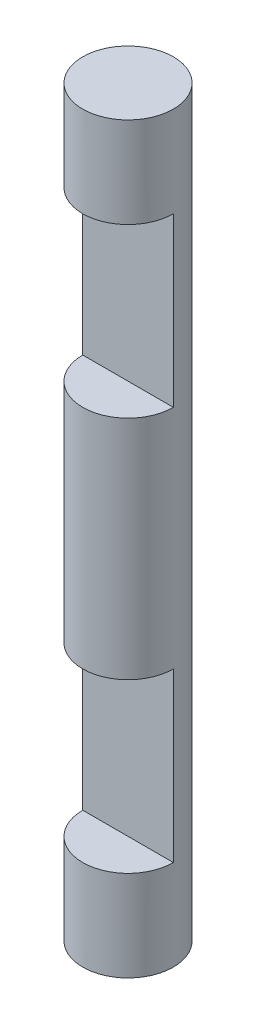
SolidWorks part; units mm, degrees
material "ABS"
ref_plane "Front Plane" through (0, 0, 0) normal (0, 0, 1) x (1, 0, 0)
ref_plane "Top Plane" through (0, 0, 0) normal (0, 1, 0) x (1, 0, 0)
ref_plane "Right Plane" through (0, 0, 0) normal (1, 0, 0) x (0, 0, -1)
sketch "Sketch1" plane through (0, 0, 0) normal (0, 1, 0) x (1, 0, 0)
  circle A0 centre (0, 0) radius 13
  dimension "D1" = 26
extrude "Boss-Extrude1" add sketch "Sketch1" along normal blind 1
ref_plane "Plane1" through (0, 1, 0) normal (0, 1, 0) x (1, 0, 0)
ref_plane "Plane2" through (0, 4.7, 0) normal (0, 1, 0) x (1, 0, 0)
ref_plane "Plane3" through (0, 9.7, 0) normal (0, 1, 0) x (1, 0, 0)
ref_plane "Plane4" through (0, 13.4, 0) normal (0, 1, 0) x (1, 0, 0)
ref_plane "Plane5" through (0, 18.4, 0) normal (0, 1, 0) x (1, 0, 0)
ref_plane "Plane6" through (0, 22.1, 0) normal (0, 1, 0) x (1, 0, 0)
ref_plane "Plane7" through (0, 27.1, 0) normal (0, 1, 0) x (1, 0, 0)
ref_plane "Plane8" through (0, 30.8, 0) normal (0, 1, 0) x (1, 0, 0)
sketch "Sketch16" plane through (0, 30.8, 0) normal (0, 1, 0) x (1, 0, 0)
  circle A0 centre (0, 0) radius 13
  circle A1 centre (0, 0) radius 13 construction
  dimension "D1" = 0
extrude "Boss-Extrude3" add sketch "Sketch16" along normal blind 1 separate body
sketch "Sketch18" plane through (0, 4.7, 0) normal (0, 1, 0) x (1, 0, 0)
  line L1 (-11, -11) -> (11, -11)
  line L2 (-11, -11) -> (-11, 11)
  line L3 (-11, 11) -> (11, 11)
  line L4 (11, -11) -> (11, 11)
  dimension "D2" = 22
  dimension "D3" = 22
sketch "Sketch19" plane through (0, 1, 0) normal (0, 1, 0) x (1, 0, 0)
  circle A0 centre (0, 11) radius 1
  point P13 (0, 0)
  dimension "D1" = 2
  dimension "D2" = 11
extrude "Boss-Extrude4" add sketch "Sketch19" along normal up to surface (29.8 mm away) up to face at (0, 30.8, 13)
extrude "Cut-Extrude6" cut sketch "Sketch18" against normal blind 3.7
sketch "Sketch21" plane through (0, 13.4, 0) normal (0, 1, 0) x (1, 0, 0)
  line L1 (-11, -11) -> (11, -11)
  line L2 (-11, -11) -> (-11, 11)
  line L3 (-11, 11) -> (11, 11)
  line L4 (11, -11) -> (11, 11)
  dimension "D1" = 11
  dimension "D2" = 22
  dimension "D3" = 22
  dimension "D4" = 11
extrude "Cut-Extrude7" cut sketch "Sketch21" against normal blind 3.7
sketch "Sketch22" plane through (0, 22.1, 0) normal (0, 1, 0) x (1, 0, 0)
  circle A0 centre (0, 0) radius 11
  dimension "D1" = 22
extrude "Cut-Extrude8" cut sketch "Sketch22" against normal blind 3.7
sketch "Sketch23" plane through (0, 30.8, 0) normal (0, 1, 0) x (1, 0, 0)
  circle A0 centre (0, 0) radius 11
  dimension "D1" = 22
extrude "Cut-Extrude9" cut sketch "Sketch23" against normal blind 3.7
sketch "Sketch24" plane through (0, 31.8, 0) normal (0, 1, 0) x (1, 0, 0)
  circle A0 centre (0, 0) radius 19.9218
extrude "Cut-Extrude10" cut sketch "Sketch24" against normal blind 1
sketch "Sketch25" plane through (0, 1, 0) normal (0, 1, 0) x (1, 0, 0)
  circle A0 centre (0, 0) radius 36.1829
extrude "Cut-Extrude11" cut sketch "Sketch25" against normal blind 1
sketch "Sketch26" plane through (0, 30.8, 0) normal (0, 1, 0) x (1, 0, 0)
  circle A0 centre (0, 11) radius 1
  arc A1 (0.999, 10.9545) -> (-0.999, 10.9545) centre (0, 0) ccw construction
  arc A2 (0.999, 10.9545) -> (-0.999, 10.9545) centre (0, 11) ccw construction
  arc M1 (0.999, 10.9545) -> (-0.999, 10.9545) centre (0, 11) ccw
  arc M2 (-0.999, 10.9545) -> (0.999, 10.9545) centre (0, 0) cw
  dimension "D1" = 0
extrude "Boss-Extrude5" add sketch "Sketch26" along normal blind 2 contours M2 M1 | A0 M2 region at (0, 30.8, -11.4161) region at (0, 30.8, -10.5675)
sketch "Sketch27" plane through (0, 1, 0) normal (0, -1, 0) x (1, 0, 0)
  circle A0 centre (0, -11) radius 1
extrude "Boss-Extrude6" add sketch "Sketch27" along normal blind 2
sketch "Sketch28" plane through (0, 32.8, 0) normal (0, 1, 0) x (1, 0, 0)
  circle A0 centre (0, 11) radius 9.6767
extrude "Cut-Extrude12" cut sketch "Sketch28" against normal offset from surface (17.4 mm away) 2 up to face at (0, 13.4, -10.5)
